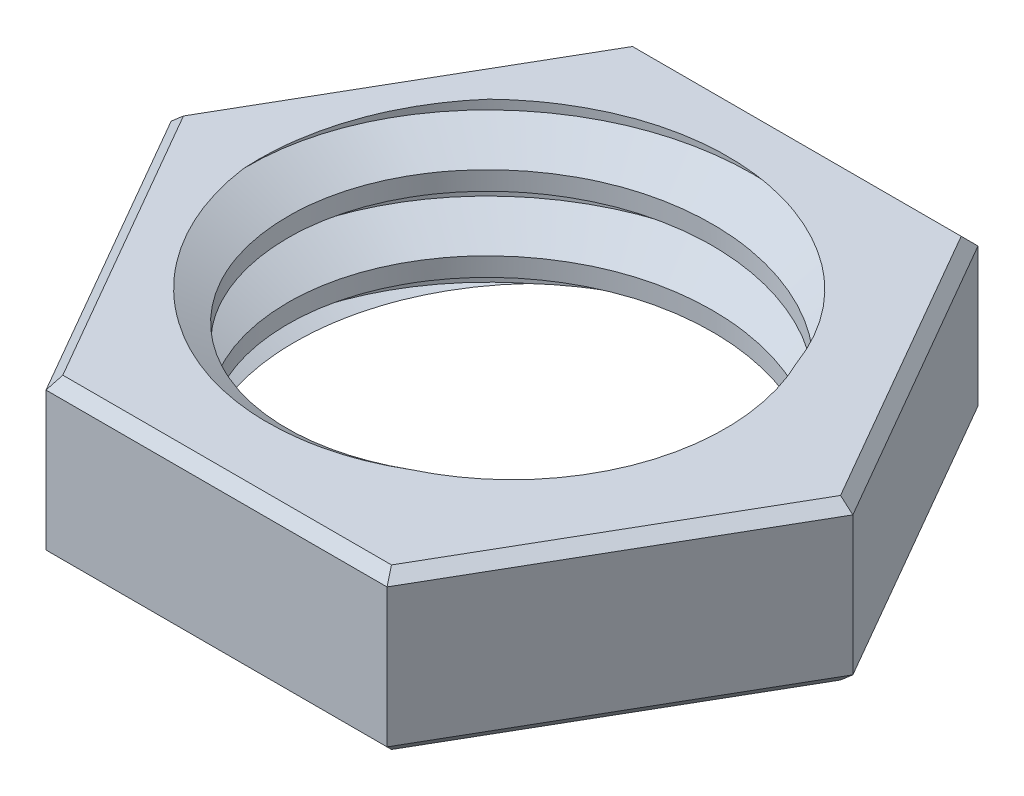
SolidWorks part; units mm, degrees
ref_plane "Front Plane" through (0, 0, 0) normal (0, 0, 1) x (1, 0, 0)
ref_plane "Top Plane" through (0, 0, 0) normal (0, 1, 0) x (1, 0, 0)
ref_plane "Right Plane" through (0, 0, 0) normal (1, 0, 0) x (0, 0, -1)
sketch "Sketch1" plane through (0, 0, 0) normal (0, 1, 0) x (1, 0, 0)
  line L0 (-4.6672, 14.1601) -> (-1.4672, 14.1601)
  line L1 (-1.4672, 14.1601) -> (0.1308, 11.3876)
  line L2 (0.1308, 11.3876) -> (-1.4692, 8.6164)
  line L3 (-1.4692, 8.6164) -> (-4.6692, 8.6164)
  line L4 (-4.6692, 8.6164) -> (-6.2672, 11.3888)
  line L5 (-6.2672, 11.3888) -> (-4.6672, 14.1601)
  line L6 (-4.6672, 14.1601) -> (-1.4692, 8.6164) construction
  line L7 (-1.4672, 14.1601) -> (-4.6692, 8.6164) construction
  circle A0 centre (-3.0682, 11.3882) radius 2
  dimension "D3" = 4
  dimension "D1" = 120
  dimension "D2" = 3.2
extrude "Boss-Extrude1" add sketch "Sketch1" along normal blind 1.5
chamfer "Chamfer1" distance 0.1 angle 45 12 edges at (-3.0672, 1.5, -14.1601) (-0.6682, 1.5, -12.7738) (-0.6692, 1.5, -10.002) (-3.0692, 1.5, -8.6164) (-5.4682, 1.5, -10.0026) (-5.4672, 1.5, -12.7744) (-5.4672, 0, -12.7744) (-3.0672, 0, -14.1601) (-0.6682, 0, -12.7738) (-0.6692, 0, -10.002) (-5.4682, 0, -10.0026) (-3.0692, 0, -8.6164)
thread "Thread1" pitch 0.7 method cut profile "Thread Profile1" start angle 0, offset 1, length 15.39, pitch 0.7, diameter 4
ref_plane "Plane1" through (-5.0682, 2.5, -11.3882) normal (0, 0, 1) x (-1, 0, 0)
sketch "Thread Profile1" plane through (-5.0682, 2.5, -11.3882) normal (0, 0, 1) x (-1, 0, 0)
  line L0 (0, 0) -> (0, 0.7) construction
  line L1 (0, 0) -> (0.3789, 0.2187)
  line L2 (0.3789, 0.2187) -> (0.3789, 0.3062)
  line L3 (0.3789, 0.3062) -> (0, 0.525)
  line L4 (0.3789, 0.2625) -> (0, 0.2625) construction
  line L11 (0, 0) -> (0, 0.525)
  point P2 (0, 0)
  dimension "Pitch" = 0.7
  dimension "Profile_Angle" = 60
  dimension "Profile_Land" = 0.0875
  dimension "Profile_Height" = 0.3789
